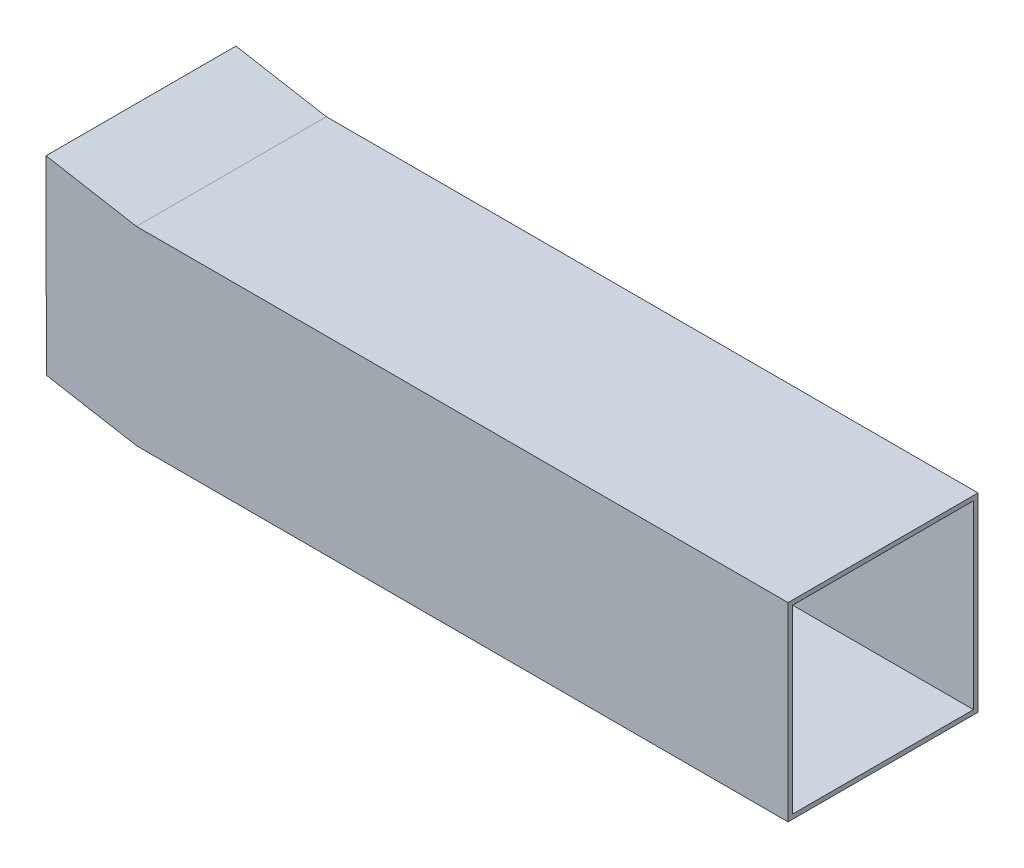
SolidWorks part; units mm, degrees
ref_plane "Front Plane" through (0, 0, 0) normal (0, 0, 1) x (1, 0, 0)
ref_plane "Top Plane" through (0, 0, 0) normal (0, 1, 0) x (1, 0, 0)
ref_plane "Right Plane" through (0, 0, 0) normal (1, 0, 0) x (0, 0, -1)
sketch "Sketch1" plane through (0, 0, 0) normal (0, 0, 1) x (1, 0, 0)
  line L0 (-260, 105) -> (-260, -105) construction
  line L1 (-410, -105) -> (410, -105)
  line L2 (-410, -105) -> (-410, 105)
  line L3 (-410, 105) -> (410, 105)
  line L4 (410, -105) -> (410, 105)
  line L5 (-410, -105) -> (410, 105) construction
  line L6 (-410, 105) -> (410, -105) construction
  point P0 (0, 0)
  dimension "D1" = 820
  dimension "D2" = 210
  dimension "D3" = 150
extrude "Boss-Extrude1" add sketch "Sketch1" along normal blind 210
sketch "Sketch2" plane through (0, 0, 210) normal (0, 0, 1) x (1, 0, 0)
  line L0 (-310, -105) -> (-310, 105) construction
  line L2 (-410, -105) -> (410, -105) construction
  line L3 (-410, 105) -> (-410, -105) construction
  line L4 (-310, -105) -> (-410, -87.3673)
  line L5 (410, 105) -> (-410, 105) construction
  line L6 (-310, 105) -> (-410, 122.6327)
  line L7 (-310, -99.9229) -> (-409.1318, -82.4433)
  line L8 (-309.1318, -100.076) -> (-409.1318, -82.4433) construction
  line L9 (-410, -87.3673) -> (-410, -105)
  line L10 (-410, -82.3673) -> (-409.1318, -82.4433)
  line L11 (-410, -105) -> (-310, -105)
  line L13 (-310.8682, 100.076) -> (-410.8682, 117.7087)
  line L14 (-410, 122.6327) -> (-410, 117.5556)
  line L15 (-310, 105) -> (-310, -105)
  line L16 (-310, -105) -> (-310.0868, -104.8924)
  line L17 (-310.8682, 100.076) -> (-310, 99.8221)
  line M3 (410, 105) -> (-410, 105)
  line M4 (-410, 105) -> (-410, -105)
  line M5 (-410, -105) -> (410, -105)
  dimension "D1" = 100
  dimension "D2" = 10
  dimension "D3" = 10
  dimension "D5" = 5
  dimension "D6" = 100
  dimension "D4" = 5
  dimension "D7" = 5
extrude "Cut-Extrude5" cut sketch "Sketch2" against normal blind 336 contours L17 L13 L10 L7 L15 M3 M4 | L4 M5 M4 region at (-376.6667, -99.1224, 210) region at (-359.3993, 6.5196, 210)
sketch "Sketch6" plane through (0, 0, 210) normal (0, 0, 1) x (1, 0, 0)
  line L0 (-310.4341, 105) -> (-410.4341, 122.6327)
  line L1 (410, 105) -> (-338.7939, 105) construction
  line L2 (-311.3024, 100.076) -> (-410.4341, 117.5556)
  line L3 (-310.4341, 105) -> (-310.4341, 99.4371)
  line L4 (-310.4341, 99.4371) -> (-311.3024, 100.076)
  line L5 (-410.4341, 122.6327) -> (-410.4341, 117.2955)
  line L6 (-311.3024, 100.076) -> (-411.3024, 117.7087) construction
  line M6 (410, 105) -> (-338.7939, 105)
  line M7 (-338.7939, 105) -> (-310.8682, 100.076)
  line M8 (-310.8682, 100.076) -> (-310, 99.8221)
  dimension "D1" = 10
  dimension "D2" = 100
  dimension "D3" = 5
extrude "Boss-Extrude2" add sketch "Sketch6" against normal through all contours L0 L5 L2 L4 L3 M8 M7 M6 region at (-366.9904, 112.5616, 210)
sketch "Sketch8" plane through (0, 0, 210) normal (0, 0, 1) x (1, 0, 0)
  line L0 (-410, -87.3673) -> (-310, -105)
  line L1 (-410.4341, 122.6327) -> (-410, -87.3673)
  line L5 (-410.4341, 122.6327) -> (-310.4341, 105)
  line L17 (-310.4341, 99.4371) -> (-310.4341, 99.949)
  line L18 (-310.4341, 99.949) -> (-310, 99.8221)
  line L19 (-310, 99.8221) -> (-310, -99.9229)
  line L20 (-310, -99.9229) -> (-409.1318, -82.4433)
  line L21 (-409.1318, -82.4433) -> (-410, -82.3673)
  line L22 (-410, -82.3673) -> (-410, -87.3673)
  line L23 (-410, -87.3673) -> (-310, -105)
  line L24 (-310, -105) -> (410, -105)
  line L25 (410, -105) -> (410, 105)
  line L26 (410, 105) -> (-310.4341, 105)
  line L27 (-310.4341, 105) -> (-410.4341, 122.6327)
  line L28 (-410.4341, 122.6327) -> (-410.4341, 117.5556)
  line L29 (-410.4341, 117.5556) -> (-311.3024, 100.076)
  line L30 (-311.3024, 100.076) -> (-310.4341, 99.4371)
  line L38 (-310, -105) -> (410, -105)
  line L39 (410, -105) -> (410, 105)
  line L40 (410, 105) -> (-310.4341, 105)
  dimension "D1" = 0
extrude "Boss-Extrude3" add sketch "Sketch8" against normal blind 5
sketch "Sketch9" plane through (0, 0, 0) normal (0, 0, -1) x (-1, 0, 0)
  line L0 (310.4341, 105) -> (310, -105)
  line L1 (310, -105) -> (410, -87.3673)
  line L2 (410, -87.3673) -> (410.4341, 122.6327)
  line L3 (410.4341, 122.6327) -> (310.4341, 105)
extrude "Boss-Extrude4" add sketch "Sketch9" against normal blind 5
shell "Shell2" thickness 5 removed face at (410, 0, 105) removed face at (-310, -0.0504, 102.5)
